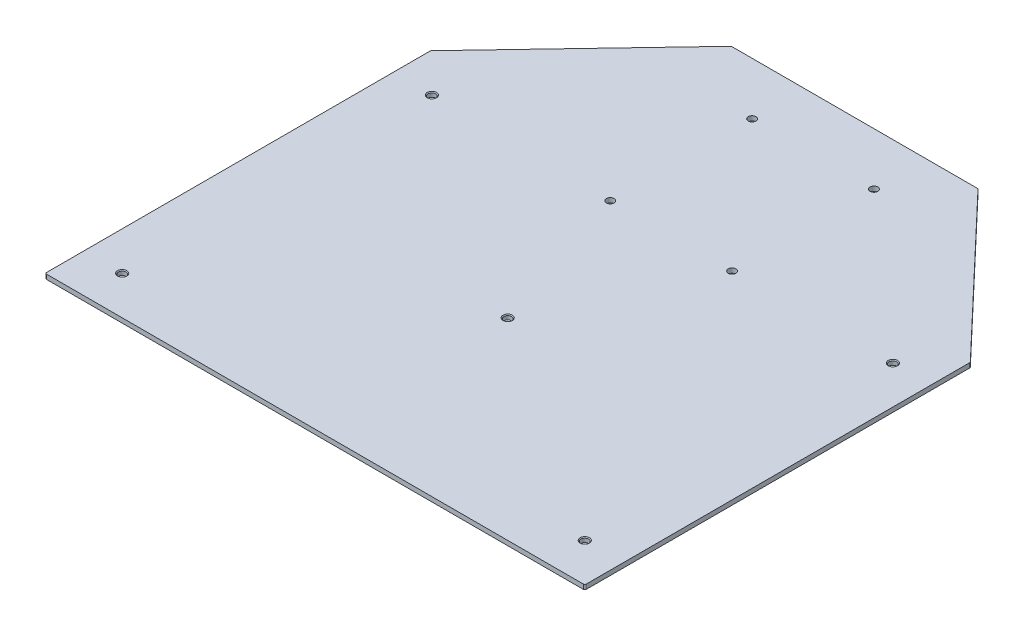
SolidWorks part; units mm, degrees
ref_plane "Front Plane" through (0, 0, 0) normal (0, 0, 1) x (1, 0, 0)
ref_plane "Top Plane" through (0, 0, 0) normal (0, 1, 0) x (1, 0, 0)
ref_plane "Right Plane" through (0, 0, 0) normal (1, 0, 0) x (0, 0, -1)
sketch "Plate Template" plane through (0, 0, 0) normal (0, 1, 0) x (1, 0, 0)
  line L0 (-79.5707, 225.0042) -> (79.5707, 225.0042)
  line L1 (-175, 125) -> (175, 125)
  line L2 (-175, 124.6007) -> (-175, -124)
  line L3 (-174, -125) -> (174, -125)
  line L4 (175, 124.6007) -> (175, -124)
  line L5 (-175, 125) -> (175, -125) construction
  line L6 (-175, -125) -> (175, 125) construction
  line L7 (-174.725, 125.2895) -> (-80.2957, 224.6929)
  line L8 (80.2957, 224.6929) -> (174.725, 125.2895)
  arc A0 (-174.725, 125.2895) -> (-175, 124.6007) centre (-174, 124.6007) ccw
  arc A1 (-175, -124) -> (-174, -125) centre (-174, -124) ccw
  arc A2 (175, -124) -> (174, -125) centre (174, -124) cw
  arc A3 (174.725, 125.2895) -> (175, 124.6007) centre (174, 124.6007) cw
  arc A4 (79.5707, 225.0042) -> (80.2957, 224.6929) centre (79.5707, 224.0042) cw
  arc A5 (-79.5707, 225.0042) -> (-80.2957, 224.6929) centre (-79.5707, 224.0042) ccw
  point P0 (0, 0)
  point P8 (0, 225.0042)
  point P9 (0, 125)
  point P24 (80, 225.0042)
  point P27 (-80, 225.0042)
  dimension "D5" = 1
  dimension "D1" = 350
  dimension "D2" = 250
  dimension "D3" = 160
  dimension "D4" = 136.47
extrude "Plate Extrude 1" add sketch "Plate Template" along normal blind 3 contours L7 A5 L0 A4 L8 A3 L4 A2 L3 A1 L2 A0
hole_wizard "M6 Tapped Hole2" positions "Sketch2" profile "Sketch3" tap size "M6" standard "ISO" end condition through all
sketch "Sketch2" plane through (0, 3, 0) normal (0, 1, 0) x (1, 0, 0)
  line L2 (-150, -100) -> (-150, -125)
  line L3 (-174, -125) -> (174, -125) construction
  line L4 (-150, -100) -> (150, -100)
  line L6 (-175, 124.6007) -> (-175, -124) construction
  line L7 (0, 0) -> (-175, 0.3004)
  line L9 (-149.6558, 100.5143) -> (150.3424, 99.4845)
  point P6 (-150, -100)
  point P15 (150, -100)
  point P20 (0, 0)
  point P27 (-149.6558, 100.5143)
  point P28 (150.3424, 99.4845)
  dimension "D1" = 25
  dimension "D2" = 300
  dimension "D3" = 25
sketch "Sketch3" plane through (-150, 3, 100) normal (1, 0, 0) x (0, 0, 1)
  line L0 (0, 0) -> (0, 3)
  line L1 (0, 3) -> (2.5, 3)
  line L2 (2.5, 3) -> (2.5, 0.525)
  line L3 (2.5, 0.525) -> (3.025, 0)
  line L5 (3.025, 0) -> (0, 0)
  line L6 (-2.5, 0.525) -> (-3.025, 0) construction
  line L11 (0, -6.35) -> (0, 107.95) construction
  dimension "Thru Tap Drill Dia." = 5
  dimension "Thru Tap Drill Depth" = 3
  dimension "Near C'Sink Dia." = 6.05
  dimension "Near C'Sink Angle" = 90
cosmetic thread "Hole Thread1" parameters "D2"=6
cosmetic thread "Hole Thread2" parameters "D2"=6
cosmetic thread "Hole Thread3" parameters "D2"=6
cosmetic thread "Hole Thread4" parameters "D2"=6
cosmetic thread "Hole Thread5" parameters "D2"=6
hole_wizard "Tap Drill for M6 Tap1" positions "Sketch4" profile "Sketch5" hole size "M6" standard "ISO"
sketch "Sketch4" plane through (0, 0, 0) normal (0, -1, 0) x (-1, 0, 0)
  line L0 (79.5707, 225.0042) -> (-79.5707, 225.0042) construction
  line L1 (175, 124.6007) -> (175, -124) construction
  point P0 (-46.5, 191.0042)
  point P3 (32.5, 191.0042)
  point P6 (32.5, 99.0042)
  point P9 (-46.5, 99.0042)
  dimension "D1" = 79
  dimension "D2" = 92
  dimension "D3" = 34
  dimension "D4" = 142.5
sketch "Sketch5" plane through (46.5, 0, -191.0042) normal (1, 0, 0) x (0, 0, -1)
  line L0 (0, 0) -> (0, 11.5022)
  line L1 (0, 11.5022) -> (2.5, 10)
  line L2 (2.5, 10) -> (2.5, 0.025)
  line L3 (2.5, 0.025) -> (2.525, 0)
  line L5 (2.525, 0) -> (0, 0)
  line L6 (-2.5, 0.025) -> (-2.525, 0) construction
  line L10 (0, 11.5022) -> (-2.5, 10) construction
  line L11 (0, -6.35) -> (0, 107.95) construction
  dimension "Hole Dia." = 5
  dimension "Hole Depth" = 10
  dimension "Near C'Sink Dia." = 5.05
  dimension "Near C'Sink Angle" = 90
  dimension "Drill Angle" = 118
sketch "Sketch6" plane through (175, 0, 0) normal (1, 0, 0) x (0, 0, -1)
  line L0 (273.7483, 216.1522) -> (-2826.7814, -507) construction
  line L1 (390.439, 315.1429) -> (-293.3988, 7.5889) construction
  line L2 (273.7483, 216.1522) -> (-2826.7814, -507) construction
  line L3 (390.439, 315.1429) -> (-293.3988, 7.5889) construction
sketch "Sketch7" plane through (0, 3, 0) normal (0, 1, 0) x (1, 0, 0)
  line L0 (-174, -125) -> (174, -125) construction
  line L1 (-174, -125) -> (174, -125)
  line L2 (0, -125) -> (-2.4409, 300.5026) construction
